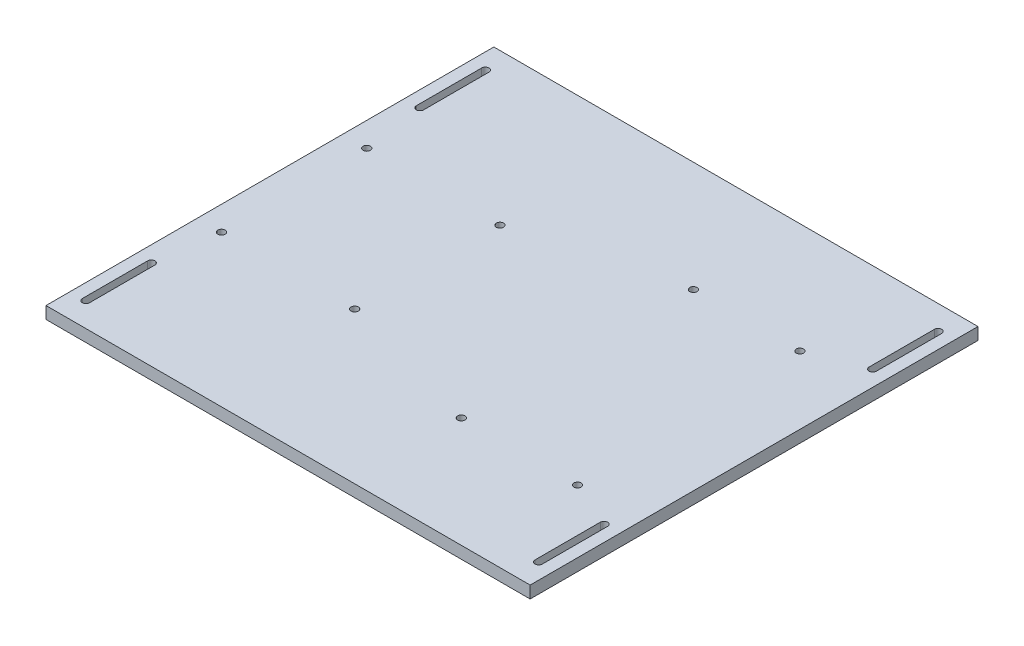
SolidWorks part; units mm, degrees
ref_plane "Front Plane" through (0, 0, 0) normal (0, 0, 1) x (1, 0, 0)
ref_plane "Top Plane" through (0, 0, 0) normal (0, 1, 0) x (1, 0, 0)
ref_plane "Right Plane" through (0, 0, 0) normal (1, 0, 0) x (0, 0, -1)
sketch "Sketch2" plane through (0, 0, 0) normal (0, 1, 0) x (1, 0, 0)
  line L0 (-93.5, 55.5) -> (-93.5, 82.5) construction
  line L1 (-100, -92.5) -> (100, -92.5)
  line L2 (-100, -92.5) -> (-100, 92.5)
  line L3 (-100, 92.5) -> (100, 92.5)
  line L4 (100, -92.5) -> (100, 92.5)
  line L5 (-100, -92.5) -> (100, 92.5) construction
  line L6 (-100, 92.5) -> (100, -92.5) construction
  line L7 (-95, 55.5) -> (-95, 82.5)
  line L8 (-92, 55.5) -> (-92, 82.5)
  line L9 (-100, 0) -> (100, 0) construction
  line L10 (100, 0) -> (0, 92.5) construction
  line L11 (0, 92.5) -> (0, -92.5) construction
  line L12 (93.5, 55.5) -> (93.5, 82.5) construction
  line L13 (95, 55.5) -> (95, 82.5)
  line L14 (92, 55.5) -> (92, 82.5)
  line L15 (93.5, -55.5) -> (93.5, -82.5) construction
  line L16 (95, -55.5) -> (95, -82.5)
  line L17 (92, -55.5) -> (92, -82.5)
  line L18 (-93.5, -55.5) -> (-93.5, -82.5) construction
  line L19 (-95, -55.5) -> (-95, -82.5)
  line L20 (-92, -55.5) -> (-92, -82.5)
  arc A0 (-95, 55.5) -> (-92, 55.5) centre (-93.5, 55.5) ccw
  arc A1 (-92, 82.5) -> (-95, 82.5) centre (-93.5, 82.5) ccw
  arc A2 (95, 55.5) -> (92, 55.5) centre (93.5, 55.5) cw
  arc A3 (92, 82.5) -> (95, 82.5) centre (93.5, 82.5) cw
  arc A4 (95, -55.5) -> (92, -55.5) centre (93.5, -55.5) ccw
  arc A5 (92, -82.5) -> (95, -82.5) centre (93.5, -82.5) ccw
  arc A6 (-95, -55.5) -> (-92, -55.5) centre (-93.5, -55.5) cw
  arc A7 (-92, -82.5) -> (-95, -82.5) centre (-93.5, -82.5) cw
  point P0 (0, 0)
  point P8 (-93.5, 69)
  point P19 (93.5, 69)
  point P26 (93.5, -69)
  point P33 (-93.5, -69)
  dimension "D4" = 1.5
  dimension "D1" = 200
  dimension "D2" = 185
  dimension "D3" = 27
  dimension "D5" = 5
  dimension "D6" = 10
extrude "Boss-Extrude1" add sketch "Sketch2" along normal blind 5
sketch "Sketch3" plane through (0, 5, 0) normal (0, 1, 0) x (1, 0, 0)
  line L0 (-100, 0) -> (100, 0) construction
  line L1 (-100, 92.5) -> (-100, -92.5) construction
  line L2 (100, -92.5) -> (100, 92.5) construction
  line L3 (100, 0) -> (0, -92.5) construction
  line L4 (-100, -92.5) -> (100, -92.5) construction
  line L5 (0, -92.5) -> (0, 92.5) construction
  line L6 (100, 92.5) -> (-100, 92.5) construction
  line L7 (-62.5, -35) -> (-62.5, 55.3864) construction
  line L8 (-30, -35) -> (-95, -35)
  line L9 (-30, -35) -> (-30, 35)
  line L10 (-30, 35) -> (-95, 35)
  line L11 (-95, -35) -> (-95, 35)
  line L12 (-30, -35) -> (-95, 35) construction
  line L13 (-30, 35) -> (-95, -35) construction
  circle A0 centre (-90, -30) radius 1.5
  circle A1 centre (-90, 30) radius 1.5
  circle A2 centre (-35, 30) radius 1.5
  circle A3 centre (-35, -30) radius 1.5
  point P9 (-62.5, 0)
  dimension "D4" = 3
  dimension "D1" = 65
  dimension "D2" = 70
  dimension "D3" = 5
  dimension "D5" = 5
  dimension "D6" = 5
extrude "Cut-Extrude1" cut sketch "Sketch3" against normal through all contours A0 | A1 | A3 | A2
sketch "Sketch4" plane through (0, 5, 0) normal (0, 1, 0) x (1, 0, 0)
  line L0 (-100, 0) -> (100, 0) construction
  line L1 (-100, 92.5) -> (-100, -92.5) construction
  line L2 (100, -92.5) -> (100, 92.5) construction
  line L3 (50, 92.5) -> (50, -92.5) construction
  line L4 (100, 92.5) -> (-100, 92.5) construction
  line L5 (-100, -92.5) -> (100, -92.5) construction
  circle A0 centre (28, 46.935) radius 1.5
  circle A1 centre (72, 46.935) radius 1.5
  circle A2 centre (26, -46.935) radius 1.5
  circle A3 centre (74, -46.935) radius 1.5
  dimension "D1" = 3
  dimension "D4" = 3
  dimension "D7" = 46.935
  dimension "D2" = 50
  dimension "D3" = 44
  dimension "D5" = 48
  dimension "D6" = 93.87
extrude "Cut-Extrude3" cut sketch "Sketch4" against normal through all
